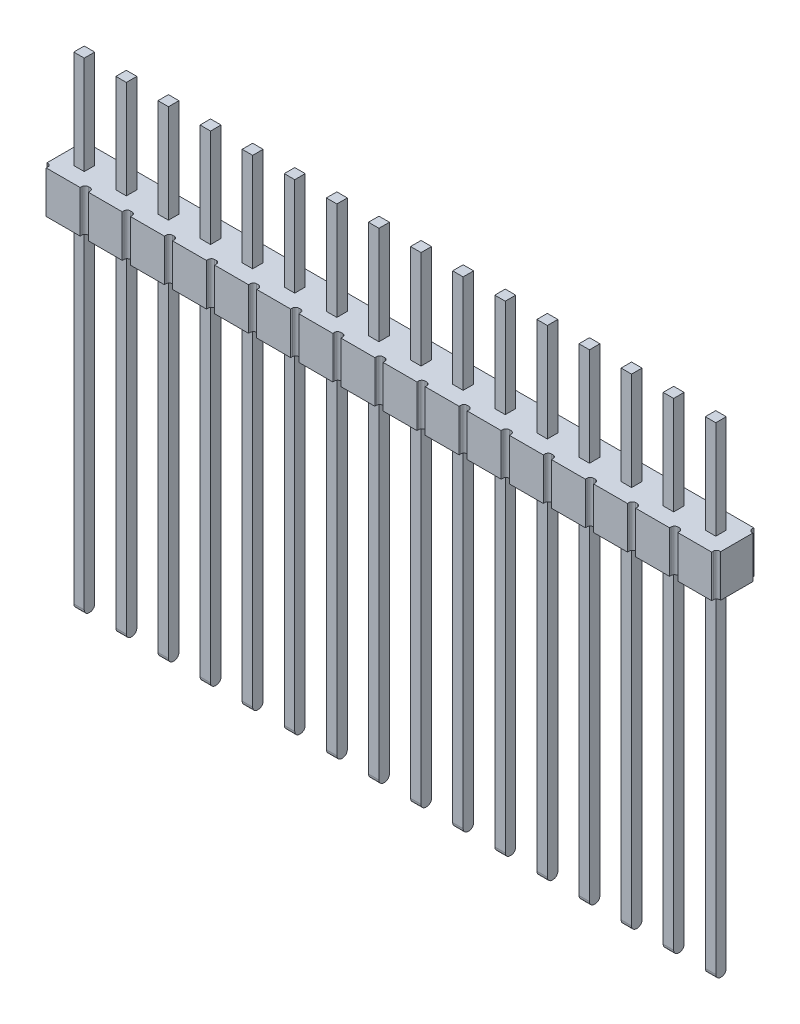
SolidWorks part; units mm, degrees
ref_plane "Front Plane" through (0, 0, 0) normal (0, 0, 1) x (1, 0, 0)
ref_plane "Top Plane" through (0, 0, 0) normal (0, 1, 0) x (1, 0, 0)
ref_plane "Right Plane" through (0, 0, 0) normal (1, 0, 0) x (0, 0, -1)
sketch "Sketch1" plane through (0, 0, 0) normal (0, 0, 1) x (1, 0, 0)
  line L0 (-20.56, 1.285) -> (20.56, 1.285)
  line L1 (-20.56, 1.285) -> (-20.56, -1.285)
  line L2 (20.56, 1.285) -> (20.56, -1.285)
  line L3 (-20.56, -1.285) -> (20.56, -1.285)
  line L4 (-20.56, 1.285) -> (20.56, -1.285) construction
  line L5 (20.56, 1.285) -> (-20.56, -1.285) construction
  point P1 (0, 0)
  dimension "D1" = 2.57
  dimension "D2" = 41.12
extrude "Boss-Extrude1" add sketch "Sketch1" along normal blind 1.285 and the other way blind 1.285
sketch "Sketch3" plane through (0, 1.285, 0) normal (0, 1, 0) x (1, 0, 0)
  line L0 (-0.05, -0.985) -> (0.05, -0.985)
  line L1 (-0.25, -1.185) -> (-0.25, -1.285)
  line L2 (0.25, -1.185) -> (0.25, -1.285)
  line L3 (-0.25, -1.285) -> (0.25, -1.285)
  line L4 (-0.25, -0.985) -> (0.25, -1.285) construction
  line L5 (0.25, -0.985) -> (-0.25, -1.285) construction
  line L8 (20.56, -1.285) -> (-20.56, -1.285) construction
  arc A0 (0.05, -0.985) -> (0.25, -1.185) centre (0.05, -1.185) cw
  arc A1 (-0.25, -1.185) -> (-0.05, -0.985) centre (-0.05, -1.185) cw
  point P1 (0, -1.135)
  dimension "D4" = 0.2
  dimension "D1" = 0.3
  dimension "D2" = 0.5
  dimension "D3" = 0
extrude "Cut-Extrude2" cut sketch "Sketch3" against normal through all
pattern_linear "LPattern2" count 9 spacing 2.57 along (-1, 0, 0) count 9 spacing 2.57 along (1, 0, 0) of "Cut-Extrude2"
mirror "Mirror2" about plane through (0, 0, 0) normal (0, 0, 1) of "LPattern2"
sketch "Sketch4" plane through (0, 1.285, 0) normal (0, 1, 0) x (1, 0, 0)
  line L0 (0.965, -0.32) -> (1.605, -0.32)
  line L1 (0.965, -0.32) -> (0.965, 0.32)
  line L2 (1.605, -0.32) -> (1.605, 0.32)
  line L3 (0.965, 0.32) -> (1.605, 0.32)
  line L4 (0.965, -0.32) -> (1.605, 0.32) construction
  line L5 (1.605, -0.32) -> (0.965, 0.32) construction
  point P1 (1.285, 0)
  dimension "D1" = 1.285
  dimension "D2" = 0
  dimension "D3" = 0.64
  dimension "D4" = 0.64
sketch "Sketch5" plane through (0, -1.285, 0) normal (0, -1, 0) x (1, 0, 0)
  line L0 (0.965, -0.32) -> (1.605, -0.32)
  line L1 (0.965, -0.32) -> (0.965, 0.32)
  line L2 (1.605, -0.32) -> (1.605, 0.32)
  line L3 (0.965, 0.32) -> (1.605, 0.32)
  line L4 (0.965, -0.32) -> (1.605, 0.32) construction
  line L5 (1.605, -0.32) -> (0.965, 0.32) construction
  point P1 (1.285, 0)
  dimension "D1" = 0.64
  dimension "D2" = 0.64
  dimension "D3" = 1.285
  dimension "D4" = 0
extrude "Boss-Extrude2" add sketch "Sketch5" along normal blind 20.9
extrude "Boss-Extrude3" add sketch "Sketch4" along normal blind 6
pattern_linear "LPattern6" count 9 spacing 2.57 along (-1, 0, 0) count 8 spacing 2.57 along (1, 0, 0) of "Boss-Extrude2", "Boss-Extrude3"
fillet "Fillet2" radius 0.3 32 edges at (1.285, -22.185, 0.32) (1.285, -22.185, -0.32) (-19.275, -22.185, -0.32) (-16.705, -22.185, -0.32) (-14.135, -22.185, -0.32) (-11.565, -22.185, -0.32) (-8.995, -22.185, -0.32) (-6.425, -22.185, -0.32) (-3.855, -22.185, -0.32) (-1.285, -22.185, -0.32) (3.855, -22.185, -0.32) (6.425, -22.185, -0.32) (8.995, -22.185, -0.32) (11.565, -22.185, -0.32) (14.135, -22.185, -0.32) (16.705, -22.185, -0.32) (19.275, -22.185, -0.32) (19.275, -22.185, 0.32) (16.705, -22.185, 0.32) (14.135, -22.185, 0.32) (11.565, -22.185, 0.32) (8.995, -22.185, 0.32) (6.425, -22.185, 0.32) (3.855, -22.185, 0.32) (-1.285, -22.185, 0.32) (-3.855, -22.185, 0.32) (-6.425, -22.185, 0.32) (-8.995, -22.185, 0.32) (-11.565, -22.185, 0.32) (-14.135, -22.185, 0.32) (-16.705, -22.185, 0.32) (-19.275, -22.185, 0.32)
